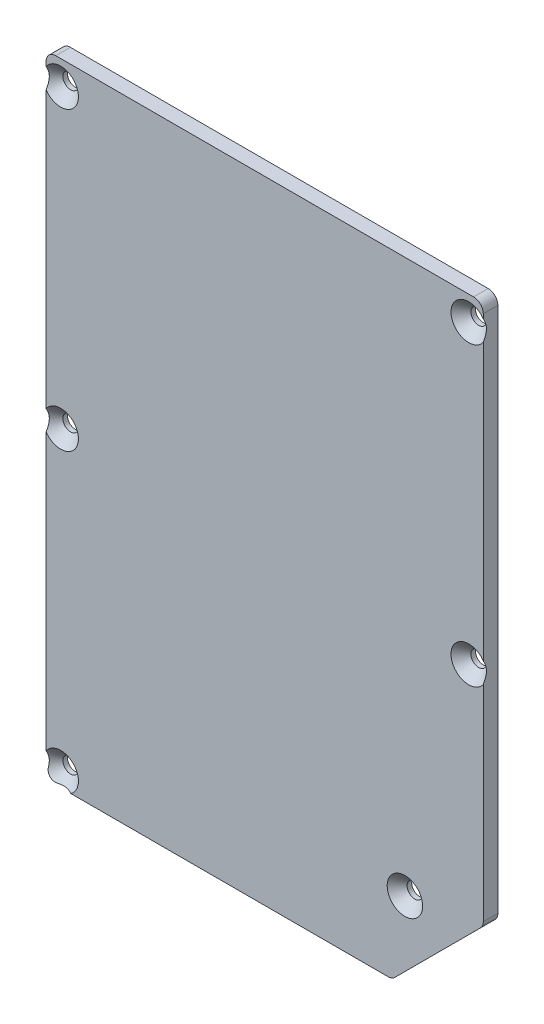
SolidWorks part; units mm, degrees
ref_plane "Front Plane" through (0, 0, 0) normal (0, 0, 1) x (1, 0, 0)
ref_plane "Top Plane" through (0, 0, 0) normal (0, 1, 0) x (1, 0, 0)
ref_plane "Right Plane" through (0, 0, 0) normal (1, 0, 0) x (0, 0, -1)
sketch "Sketch1" plane through (0, 0, 0) normal (0, 0, 1) x (1, 0, 0)
  line B0 (-43, 70) -> (43, 70)
  line B1 (-45, 68) -> (-45, -58)
  line B2 (-43, -60) -> (25.3848, -60)
  line B3 (45, 68) -> (45, -40.3848)
  line B4 (44.4142, -41.799) -> (26.799, -59.4142)
  arc B5 (-43, -60) -> (-45, -58) centre (-43, -58) cw
  arc B6 (45, 68) -> (43, 70) centre (43, 68) ccw
  arc B7 (-43, 70) -> (-45, 68) centre (-43, 68) ccw
  arc B8 (45, -40.3848) -> (44.4142, -41.799) centre (43, -40.3848) cw
  arc B9 (26.799, -59.4142) -> (25.3848, -60) centre (25.3848, -58) cw
sketch_block_instance "Block-B01_block_lid-1"
sketch_block "Block-B01_block_lid"
extrude "Boss-Extrude1" add sketch "Sketch1" along normal blind 3
sketch "Sketch5" plane through (0, 0, 3) normal (0, 0, 1) x (1, 0, 0)
  point P0 (-42, 65)
  point P1 (42, 65)
  point P3 (42, 4)
  point P5 (28.864, -43.864)
  point P7 (-42, -57)
  point P9 (-42, 4)
  point P11 (-42, 65)
hole_wizard "CSK for M3 Countersunk Flat Head Screw1" positions "3DSketch3" profile "Sketch6" countersink size "M3" standard "ISO"
sketch3d "3DSketch3"
  point P0 (-42, -57, 3)
  point P3 (28.864, -43.864, 3)
  point P6 (42, 4, 3)
  point P9 (-42, 4, 3)
  point P12 (-42, 65, 3)
  point P15 (42, 65, 3)
sketch "Sketch6" plane through (-42, -57, 3) normal (1, 0, 0) x (0, -1, 0)
  line L0 (0, 0) -> (0, 5.9614)
  line L1 (0, 5.9614) -> (1.6, 5)
  line L2 (1.6, 5) -> (1.6, 2.05)
  line L3 (1.6, 2.05) -> (3.65, 0)
  line L5 (3.65, 0) -> (0, 0)
  line L6 (-1.6, 2.05) -> (-3.65, 0) construction
  line L10 (0, 5.9614) -> (-1.6, 5) construction
  line L11 (0, -6.35) -> (0, 107.95) construction
  dimension "Hole Dia." = 3.2
  dimension "Hole Depth" = 5
  dimension "Near C'Sink Dia." = 7.3
  dimension "Near C'Sink Angle" = 90
  dimension "Drill Angle" = 118
